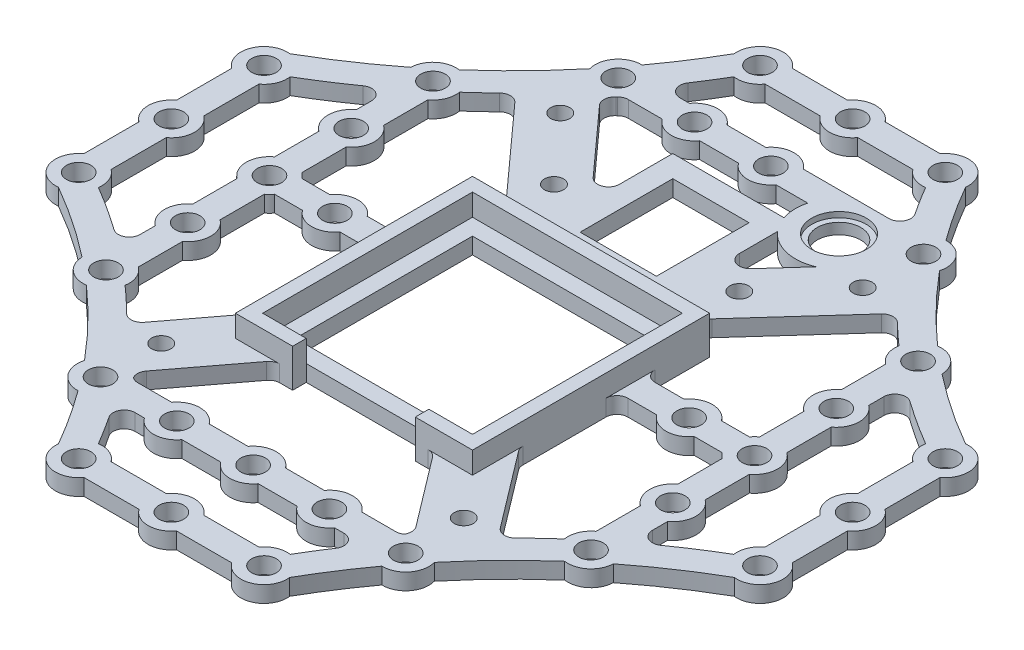
SolidWorks part; units mm, degrees
ref_plane "Front Plane" through (0, 0, 0) normal (0, 0, 1) x (1, 0, 0)
ref_plane "Top Plane" through (0, 0, 0) normal (0, 1, 0) x (1, 0, 0)
ref_plane "Right Plane" through (0, 0, 0) normal (1, 0, 0) x (0, 0, -1)
sketch "Sketch1" plane through (0, 0, 0) normal (0, 1, 0) x (1, 0, 0)
  line L0 (-32, 0) -> (32, 0) construction
  line L1 (-32, 41) -> (32, 41)
  line L2 (-32, 41) -> (-32, -41)
  line L3 (-32, -41) -> (32, -41)
  line L4 (32, 41) -> (32, -41)
  line L5 (-32, 41) -> (32, -41) construction
  line L6 (-32, -41) -> (32, 41) construction
  line L7 (0, 41) -> (0, -41) construction
  circle A0 centre (27.75, -36.6) radius 1.75
  circle A1 centre (-27.75, -36.6) radius 1.75
  circle A2 centre (27.75, 36.6) radius 1.75
  circle A3 centre (-27.75, 36.6) radius 1.75
  point P0 (0, 0)
  dimension "D3" = 3.5
  dimension "D1" = 64
  dimension "D2" = 82
  dimension "D4" = 27.75
  dimension "D5" = 36.6
extrude "Boss-Extrude1" add sketch "Sketch1" along normal blind 3
sketch "Sketch2" plane through (0, 3, 0) normal (0, 1, 0) x (1, 0, 0)
  line L0 (0, 41) -> (0, -41) construction
  line L1 (32, 41) -> (-32, 41) construction
  line L2 (-32, -41) -> (32, -41) construction
  line L3 (-32, 0) -> (32, 0) construction
  line L4 (-32, 41) -> (-32, -41) construction
  line L5 (32, -41) -> (32, 41) construction
  line L6 (-11.25, -26.5) -> (-11.25, -29)
  line L7 (-19.25, 12) -> (19.25, 12)
  line L8 (-19.25, 12) -> (-19.25, -26.5)
  line L9 (-19.25, -26.5) -> (-11.25, -26.5)
  line L10 (19.25, 12) -> (19.25, -26.5)
  line L11 (-19.25, 12) -> (19.25, -26.5) construction
  line L12 (-19.25, -26.5) -> (19.25, 12) construction
  line L13 (-21.75, 14.5) -> (21.75, 14.5)
  line L14 (-21.75, 14.5) -> (-21.75, -29)
  line L15 (-21.75, -29) -> (-11.25, -29)
  line L16 (21.75, 14.5) -> (21.75, -29)
  line L17 (-21.75, 14.5) -> (21.75, -29) construction
  line L18 (-21.75, -29) -> (21.75, 14.5) construction
  line L19 (11.25, -26.5) -> (11.25, -29)
  line L20 (11.25, -26.5) -> (19.25, -26.5)
  line L21 (11.25, -29) -> (21.75, -29)
  point P12 (0, -7.25)
  point P17 (0, -7.25)
  point P19 (0, -7.25)
  dimension "D1" = 38.5
  dimension "D2" = 2.5
  dimension "D3" = 12
  dimension "D4" = 8
  dimension "D5" = 8
extrude "GPS-Housing" add sketch "Sketch2" along normal blind 4
sketch "Sketch3" plane through (0, 3, 0) normal (0, 1, 0) x (1, 0, 0)
  line L0 (-32, 24.7) -> (32, 24.7) construction
  line L1 (-32, 41) -> (-32, -41) construction
  line L2 (32, -41) -> (32, 41) construction
  line L3 (0, 41) -> (0, 6.6316) construction
  line L6 (21.75, 14.5) -> (-21.75, 14.5) construction
  line L7 (32, 41) -> (-32, 41) construction
  circle A0 centre (-17, 24.7) radius 1.75
  circle A1 centre (17, 24.7) radius 1.75
  dimension "D1" = 3.5
  dimension "D2" = 10.2
  dimension "D3" = 17
extrude "Spectrum-Cover-Hole" cut sketch "Sketch3" against normal through all
sketch "Sketch6" plane through (0, 3, 0) normal (0, 1, 0) x (1, 0, 0)
  line L0 (0, 41) -> (0, -41) construction
  line L1 (32, 41) -> (-32, 41) construction
  line L2 (-32, -41) -> (32, -41) construction
  line L3 (-32, 0) -> (32, 0) construction
  line L4 (-32, 41) -> (-32, -41) construction
  line L5 (32, -41) -> (32, 41) construction
  line L6 (0, 0) -> (116.6726, -116.6726) construction
  line L7 (0, -41) -> (0, -155.7646) construction
  line L8 (32, 0) -> (119.0429, 0) construction
  line L9 (65, 19.5647) -> (65, -19.5647)
  line L10 (-19.5647, -65) -> (19.5647, -65)
  line L11 (-65, 19.5647) -> (-65, -19.5647)
  line L12 (-19.5647, 65) -> (19.5647, 65)
  line L14 (-32, 41) -> (32, 41)
  line L15 (32, 41) -> (32, -41)
  line L16 (32, -41) -> (-32, -41)
  line L17 (-32, -41) -> (-32, 41)
  arc A0 (65, -19.5647) -> (19.5647, -65) centre (116.6726, -116.6726) ccw
  circle A1 centre (116.6726, -116.6726) radius 110 construction
  arc A2 (-65, -19.5647) -> (-19.5647, -65) centre (-116.6726, -116.6726) cw
  arc A3 (65, 19.5647) -> (19.5647, 65) centre (116.6726, 116.6726) cw
  arc A4 (-65, 19.5647) -> (-19.5647, 65) centre (-116.6726, 116.6726) ccw
  point P24 (0, -65)
  point P28 (116.6726, -116.6726)
  point P30 (65, 0)
  point P36 (-65, 0)
  dimension "D9" = 220
  dimension "D1" = 45
  dimension "D2" = 65
  dimension "D3" = 65
  dimension "D4" = 165
extrude "Extension" add sketch "Sketch6" against normal blind 3
sketch "Sketch7" plane through (0, 3, 0) normal (0, 1, 0) x (1, 0, 0)
  line L1 (65, 0) -> (-65, 0) construction
  line L2 (65, -19.5647) -> (65, 19.5647) construction
  line L3 (-65, 19.5647) -> (-65, -19.5647) construction
  line L4 (0, 65) -> (0, -65) construction
  line L5 (19.5647, 65) -> (-19.5647, 65) construction
  line L6 (-19.5647, -65) -> (19.5647, -65) construction
  line L8 (0, -60) -> (16.6066, -60)
  line L9 (60, -19.5647) -> (60, 19.5647)
  line L10 (60, -16.6066) -> (60, 0)
  line L11 (-60, 0) -> (-60, -16.6066)
  line L12 (-16.6066, -60) -> (0, -60)
  line L13 (0, 60) -> (-16.6066, 60)
  line L14 (-60, 16.6066) -> (-60, 0)
  line L15 (60, 0) -> (60, 16.6066)
  line L16 (16.6066, 60) -> (0, 60)
  line L18 (47, 25.1809) -> (47, -25.1809)
  line L19 (42, 29.2141) -> (42, -29.2141)
  line L20 (21.75, -20.4107) -> (34.0707, -36.6606)
  line L21 (60, 2.5) -> (60, -2.5)
  line L24 (0, 0) -> (27.75, -36.6) construction
  line L25 (21.75, -29) -> (21.75, 14.5) construction
  line L26 (14.608, -29) -> (26.7391, -45)
  line L27 (11.25, -29) -> (21.75, -29) construction
  line L28 (-22.9722, -50) -> (22.9722, -50)
  line L29 (-26.7391, -45) -> (26.7391, -45)
  line L30 (-10.8771, 43.5) -> (12.4237, 43.5) construction
  line L31 (21.75, 14.5) -> (-21.75, 14.5) construction
  line L32 (-47, 25.1809) -> (-47, -25.1809)
  line L33 (-42, 29.2141) -> (-42, -29.2141)
  line L34 (-21.75, -20.4107) -> (-34.0707, -36.6606)
  line L35 (-14.608, -29) -> (-26.7391, -45)
  line L36 (15.8714, 14.5) -> (35.0176, 35.6944)
  line L37 (-15.8714, 14.5) -> (-35.0176, 35.6944)
  line L38 (-22.9722, 50) -> (22.9722, 50)
  line L39 (-7, 36.5) -> (7, 36.5)
  line L40 (-7, 36.5) -> (-7, 19.5)
  line L41 (-7, 19.5) -> (7, 19.5)
  line L42 (7, 36.5) -> (7, 19.5)
  line L43 (-7, 36.5) -> (7, 19.5) construction
  line L44 (-7, 19.5) -> (7, 36.5) construction
  line L45 (-26.7391, 45) -> (26.7391, 45)
  line L46 (-19.25, 12) -> (19.25, 12) construction
  line L47 (-16.25, 9) -> (16.25, 9)
  line L48 (-16.25, 9) -> (-16.25, -23.5)
  line L49 (-16.25, -23.5) -> (-11.25, -23.5)
  line L50 (16.25, 9) -> (16.25, -23.5)
  line L51 (-19.25, -26.5) -> (-19.25, 12) construction
  line L52 (19.25, 12) -> (19.25, -26.5) construction
  line L53 (19.25, -26.5) -> (11.25, -26.5) construction
  line L54 (-11.25, -29) -> (-11.25, -23.5)
  line L55 (11.25, -29) -> (11.25, -23.5)
  line L57 (11.25, -23.5) -> (16.25, -23.5)
  line L58 (-21.75, 14.5) -> (-21.75, -29) construction
  line L59 (-42, 2.5) -> (-21.75, 2.5)
  line L60 (-42, 2.5) -> (-42, -2.5)
  line L61 (-42, -2.5) -> (-21.75, -2.5)
  line L62 (-21.75, 2.5) -> (-21.75, -2.5)
  line L63 (42, -2.5) -> (21.75, -2.5)
  line L64 (42, 2.5) -> (21.75, 2.5)
  line L65 (21.75, 14.5) -> (-21.75, 14.5) construction
  line L66 (27.75, 36.6) -> (17, 24.7) construction
  line L67 (15.8714, 14.5) -> (21.75, 14.5)
  line L68 (21.75, 14.5) -> (21.75, 2.5)
  line L69 (-15.8714, 14.5) -> (-21.75, 14.5)
  line L70 (-21.75, 14.5) -> (-21.75, 2.5)
  line L71 (-11.25, -23.5) -> (11.25, -23.5)
  line L72 (-11.25, -26.5) -> (11.25, -26.5)
  arc A6 (62.6512, -15.1507) -> (15.1507, -62.6512) centre (116.6726, -116.6726) ccw
  arc A7 (60, -16.6066) -> (16.6066, -60) centre (116.6726, -116.6726) ccw
  arc A8 (-16.6066, -60) -> (-60, -16.6066) centre (-116.6726, -116.6726) ccw
  arc A9 (-60, 16.6066) -> (-16.6066, 60) centre (-116.6726, 116.6726) ccw
  arc A10 (16.6066, 60) -> (60, 16.6066) centre (116.6726, 116.6726) ccw
  point P45 (0, 0)
  point P73 (0, 28)
  line M3 (21.75, 14.5) -> (21.75, -29)
  line M4 (21.75, -29) -> (11.25, -29)
  line M5 (11.25, -29) -> (11.25, -26.5)
  line M11 (-11.25, -26.5) -> (-11.25, -29)
  line M12 (-11.25, -29) -> (-21.75, -29)
  line M13 (-21.75, -29) -> (-21.75, 14.5)
  line M20 (-21.75, 14.5) -> (21.75, 14.5)
  dimension "D1" = 5
  dimension "D4" = 2.5
  dimension "D2" = 42
  dimension "D3" = 5
  dimension "D5" = 10
  dimension "D8" = 5
  dimension "D10" = 5
  dimension "D11" = 29
  dimension "D12" = 5
  dimension "D13" = 7
  dimension "D14" = 14
  dimension "D15" = 5
  dimension "D16" = 10
  dimension "D17" = 3
  dimension "D18" = 3
  dimension "D19" = 3
  dimension "D20" = 3
  dimension "D21" = 2.5
  dimension "D22" = 6
  dimension "D6" = 5
  dimension "D7" = 5
  dimension "D9" = 4
extrude "Weight-Reducer" cut sketch "Sketch7" against normal through all contours A10 L16 L13 A9 L38 | A10 L18 A7 L10 L15 | A8 L12 L8 A7 L28 | A9 L14 L11 A8 L32 | L42 L39 L40 L41 | L55 L57 L50 L47 L48 L49 L54 L35 L29 L26 M11 M12 M4 M5 | A8 L34 L61 L33 M13 | A7 L19 L63 L20 M3 | A10 L36 L64 L19 M20 M3 | A9 L33 L59 L37 M13 M20 | L49 L71 L57 L50 L47 L48 region at (0, 3, 54.7305) region at (0, 3, 36.9962) region at (32.5447, 3, 16.7096) region at (-32.5447, 3, 16.7096) region at (53.0515, 3, 0) region at (-53.0515, 3, 0) region at (0, 3, 7.25) region at (32.1272, 3, -16.4309) region at (-32.1272, 3, -16.4309) region at (0, 3, -54.7305) region at (0, 3, -28)
sketch "Sketch8" plane through (0, 3, 0) normal (0, 1, 0) x (1, 0, 0)
  line L1 (0, 0) -> (0, 68.176) construction
  line L2 (-77.2406, 0) -> (92.1007, 0) construction
  circle A0 centre (17, 43) radius 4
  dimension "D1" = 8
  dimension "D2" = 17
  dimension "D3" = 43
extrude "Arm-Button-Hole" cut sketch "Sketch8" against normal through all
sketch "Sketch9" plane through (0, 3, 0) normal (0, 1, 0) x (1, 0, 0)
  circle A0 centre (17, 43) radius 5
  dimension "D1" = 10
extrude "Arm-Button-Hole-LG" cut sketch "Sketch9" against normal blind 1
sketch "Sketch11" plane through (0, 3, 0) normal (0, 1, 0) x (1, 0, 0)
  line L0 (-27.75, 36.6) -> (-17, 24.7) construction
  line L1 (-27.6172, 43.9119) -> (-11, 25.517)
  line L2 (-11, 25.517) -> (-11, 40.5)
  line L3 (-11, 40.5) -> (9.4007, 40.5)
  line L4 (-26.7391, 45) -> (9.254, 45)
  line L5 (27.75, 36.6) -> (17, 24.7) construction
  line L6 (-22.9722, 50) -> (22.9722, 50) construction
  line L7 (-7, 36.5) -> (7, 36.5) construction
  line L8 (-7, 36.5) -> (-7, 19.5) construction
  line L9 (11, 37.7085) -> (11, 25.517)
  line L10 (11, 25.517) -> (20.1506, 35.6465)
  line L11 (7, 36.5) -> (7, 19.5) construction
  arc A2 (-62.6512, 15.1507) -> (-15.1507, 62.6512) centre (-116.6726, 116.6726) ccw
  arc A3 (-27.6172, 43.9119) -> (-26.7391, 45) centre (-116.6726, 116.6726) ccw
  arc A4 (11, 37.7085) -> (20.1506, 35.6465) centre (17, 43) ccw
  circle A5 centre (17, 43) radius 8
  arc A6 (9.254, 45) -> (9.4007, 40.5) centre (17, 43) ccw
  dimension "D2" = 5
  dimension "D3" = 5
  dimension "D4" = 4
  dimension "D5" = 4
  dimension "D7" = 4
  dimension "D8" = 5
  dimension "D1" = 5
  dimension "D6" = 3
extrude "Weight-Reducer2" cut sketch "Sketch11" against normal through all
sketch "Sketch12" plane through (0, 3, 0) normal (0, 1, 0) x (1, 0, 0)
  line L0 (-65, 0) -> (65, 0) construction
  line L3 (0, 65) -> (0, -65) construction
  line L4 (19.5647, 65) -> (-19.5647, 65) construction
  line L5 (-19.5647, -65) -> (19.5647, -65) construction
  line L6 (-65, 19.5647) -> (-65, -19.5647) construction
  line L8 (65, -19.5647) -> (65, 19.5647) construction
  line L9 (62.5, 27.8761) -> (62.5, -28.3487) construction
  line L10 (44.5, 40.0562) -> (44.5, -38.8909) construction
  line L11 (47, 25.1809) -> (47, -25.1809) construction
  line L12 (-43.7279, -47.5) -> (38.8791, -47.5) construction
  line L13 (-26.7391, -45) -> (26.7391, -45) construction
  circle A0 centre (62.5, 0) radius 2.25
  circle A1 centre (62.5, 17) radius 2.25
  circle A2 centre (62.5, -17) radius 2.25
  circle A3 centre (44.5, 30) radius 2.25
  circle A4 centre (44.5, 15) radius 2.25
  circle A5 centre (44.5, 0) radius 2.25
  circle A6 centre (44.5, -15) radius 2.25
  circle A7 centre (44.5, -30) radius 2.25
  circle A8 centre (32.5, 0) radius 2.25
  circle A9 centre (0, -47.5) radius 2.25
  circle A10 centre (-14, -47.5) radius 2.25
  circle A11 centre (-28, -47.5) radius 2.25
  circle A12 centre (14, -47.5) radius 2.25
  circle A13 centre (28, -47.5) radius 2.25
  circle A14 centre (28, 47.5) radius 2.25
  circle A15 centre (-17, -62.5) radius 2.25
  circle A16 centre (0, -62.5) radius 2.25
  circle A17 centre (17, -62.5) radius 2.25
  circle A18 centre (-32.5, 0) radius 2.25
  circle A19 centre (-44.5, 0) radius 2.25
  circle A20 centre (-44.5, -15) radius 2.25
  circle A21 centre (-44.5, -30) radius 2.25
  circle A22 centre (-44.5, 15) radius 2.25
  circle A23 centre (-44.5, 30) radius 2.25
  circle A24 centre (-62.5, 17) radius 2.25
  circle A25 centre (-62.5, 0) radius 2.25
  circle A26 centre (-62.5, -17) radius 2.25
  circle A28 centre (0, 47.5) radius 2.25
  circle A29 centre (-14, 47.5) radius 2.25
  circle A30 centre (-28, 47.5) radius 2.25
  circle A33 centre (17, 62.5) radius 2.25
  circle A34 centre (0, 62.5) radius 2.25
  circle A35 centre (-17, 62.5) radius 2.25
  circle A36 centre (0, 32.5) radius 2.25 [skipped]
  circle A37 centre (0, -32.5) radius 2.25 [skipped]
  circle A38 centre (-30, -44.5) radius 2.25 [skipped]
  circle A39 centre (-15, -44.5) radius 2.25 [skipped]
  circle A40 centre (0, -44.5) radius 2.25 [skipped]
  circle A41 centre (15, -44.5) radius 2.25 [skipped]
  circle A42 centre (30, -44.5) radius 2.25 [skipped]
  circle A43 centre (-30, 44.5) radius 2.25 [skipped]
  circle A44 centre (-15, 44.5) radius 2.25 [skipped]
  circle A45 centre (0, 44.5) radius 2.25 [skipped]
  circle A46 centre (15, 44.5) radius 2.25 [skipped]
  circle A47 centre (30, 44.5) radius 2.25 [skipped]
  point P14 (62.5, 0)
  point P94 (0, 0)
  dimension "D2" = 4.5
  dimension "D3" = 4.5
  dimension "D6" = 4.5
  dimension "D7" = 4.5
  dimension "D8" = 4.5
  dimension "D11" = 4.5
  dimension "D15" = 4.5
  dimension "D16" = 4.5
  dimension "D17" = 4.5
  dimension "D1" = 2.5
  dimension "D4" = 17
  dimension "D5" = 2.5
  dimension "D9" = 15
  dimension "D10" = 30
  dimension "D12" = 12
  dimension "D14" = 2.5
  dimension "D18" = 14
  dimension "D19" = 28
  dimension "D13" = 4
extrude "Marker-Holes" cut sketch "Sketch12" against normal through all
sketch "Sketch13" plane through (0, 3, 0) normal (0, 1, 0) x (1, 0, 0)
  line L4 (-65, 0) -> (62.5, 0) construction
  line L5 (-65, 19.5647) -> (-65, -19.5647) construction
  line L6 (0, 62.5) -> (0, -62.5) construction
  circle A0 centre (62.5, 0) radius 4.25
  circle A1 centre (62.5, 0) radius 2.25 construction
  circle A2 centre (62.5, 17) radius 4.25
  circle A3 centre (62.5, 17) radius 2.25 construction
  circle A4 centre (62.5, 17) radius 2.25
  circle A5 centre (62.5, -17) radius 2.25
  circle A6 centre (62.5, -17) radius 4.25
  circle A7 centre (44.5, 30) radius 4.25
  circle A8 centre (44.5, 30) radius 2.25 construction
  circle A9 centre (44.5, 30) radius 2.25
  circle A10 centre (44.5, 15) radius 4.25
  circle A11 centre (44.5, 15) radius 2.25
  circle A12 centre (44.5, 0) radius 4.25
  circle A13 centre (44.5, 0) radius 2.25
  circle A14 centre (44.5, -15) radius 4.25
  circle A15 centre (44.5, -15) radius 2.25
  circle A16 centre (44.5, -30) radius 4.25
  circle A17 centre (44.5, -30) radius 2.25
  circle A18 centre (32.5, 0) radius 4.25
  circle A19 centre (32.5, 0) radius 2.25 construction
  circle A20 centre (32.5, 0) radius 2.25
  circle A21 centre (62.5, 0) radius 2.25
  circle A22 centre (17, -62.5) radius 4.25
  circle A23 centre (17, -62.5) radius 2.25
  circle A24 centre (0, -62.5) radius 2.25
  circle A25 centre (0, -62.5) radius 4.25
  circle A26 centre (-17, -62.5) radius 2.25
  circle A27 centre (-17, -62.5) radius 4.25
  circle A28 centre (-62.5, -17) radius 4.25
  circle A29 centre (-62.5, -17) radius 2.25
  circle A30 centre (-62.5, 0) radius 2.25
  circle A31 centre (-62.5, 0) radius 4.25
  circle A32 centre (-62.5, 17) radius 2.25
  circle A33 centre (-62.5, 17) radius 4.25
  circle A34 centre (-17, 62.5) radius 4.25
  circle A35 centre (-17, 62.5) radius 2.25
  circle A36 centre (0, 62.5) radius 2.25
  circle A37 centre (0, 62.5) radius 4.25
  circle A38 centre (17, 62.5) radius 2.25
  circle A39 centre (17, 62.5) radius 4.25
  circle A40 centre (-32.5, 0) radius 2.25
  circle A41 centre (-32.5, 0) radius 4.25
  circle A42 centre (-44.5, -30) radius 2.25
  circle A43 centre (-44.5, -30) radius 4.25
  circle A44 centre (-44.5, -15) radius 2.25
  circle A45 centre (-44.5, -15) radius 4.25
  circle A46 centre (-44.5, 0) radius 2.25
  circle A47 centre (-44.5, 0) radius 4.25
  circle A48 centre (-44.5, 15) radius 2.25
  circle A49 centre (-44.5, 15) radius 4.25
  circle A50 centre (-44.5, 30) radius 2.25
  circle A51 centre (-44.5, 30) radius 4.25
  circle A52 centre (-28, -47.5) radius 4.25
  circle A53 centre (-28, -47.5) radius 2.25 construction
  circle A54 centre (-28, -47.5) radius 2.25
  circle A55 centre (-14, -47.5) radius 4.25
  circle A56 centre (-14, -47.5) radius 2.25
  circle A57 centre (0, -47.5) radius 4.25
  circle A58 centre (0, -47.5) radius 2.25
  circle A59 centre (14, -47.5) radius 4.25
  circle A60 centre (14, -47.5) radius 2.25
  circle A61 centre (28, -47.5) radius 4.25
  circle A62 centre (28, -47.5) radius 2.25
  circle A63 centre (28, 47.5) radius 2.25
  circle A64 centre (28, 47.5) radius 4.25
  circle A65 centre (0, 47.5) radius 4.25
  circle A66 centre (0, 47.5) radius 2.25
  circle A67 centre (-14, 47.5) radius 2.25
  circle A68 centre (-14, 47.5) radius 4.25
  circle A69 centre (-28, 47.5) radius 2.25
  circle A70 centre (-28, 47.5) radius 4.25
  point P73 (0, 0)
  dimension "D1" = 8.5
  dimension "D2" = 8.5
  dimension "D3" = 8.5
  dimension "D5" = 8.5
  dimension "D7" = 8.5
  dimension "D4" = 5
  dimension "D8" = 5
  dimension "D6" = 4
extrude "Boss-Extrude3" add sketch "Sketch13" against normal blind 3
fillet "Fillet1" radius 2 30 edges at (11, 1.5, -25.517) (-11, 1.5, -25.517) (-24.5631, 1.5, -45) (-27.1053, 1.5, -43.3452) (24.5631, 1.5, 45) (25.8535, 1.5, 43.8319) (-24.5631, 1.5, 45) (-25.8535, 1.5, 43.8319) (22.9722, 1.5, 50) (-22.9722, 1.5, 50) (22.9722, 1.5, -50) (-22.9722, 1.5, -50) (21.75, 1.5, 2.5) (21.75, 1.5, -2.5) (-21.75, 1.5, 2.5) (-21.75, 1.5, -2.5) (47, 1.5, 25.1809) (-47, 1.5, 25.1809) (-47, 1.5, -25.1809) (47, 1.5, -25.1809) (-34.0707, 1.5, 36.6606) (34.0707, 1.5, 36.6606) (-35.0176, 1.5, -35.6944) (-21.75, 1.5, 20.4107) (-14.608, 1.5, 29) (14.608, 1.5, 29) (21.75, 1.5, 20.4107) (-15.8714, 1.5, -14.5) (15.8714, 1.5, -14.5) (35.0176, 1.5, -35.6944)
